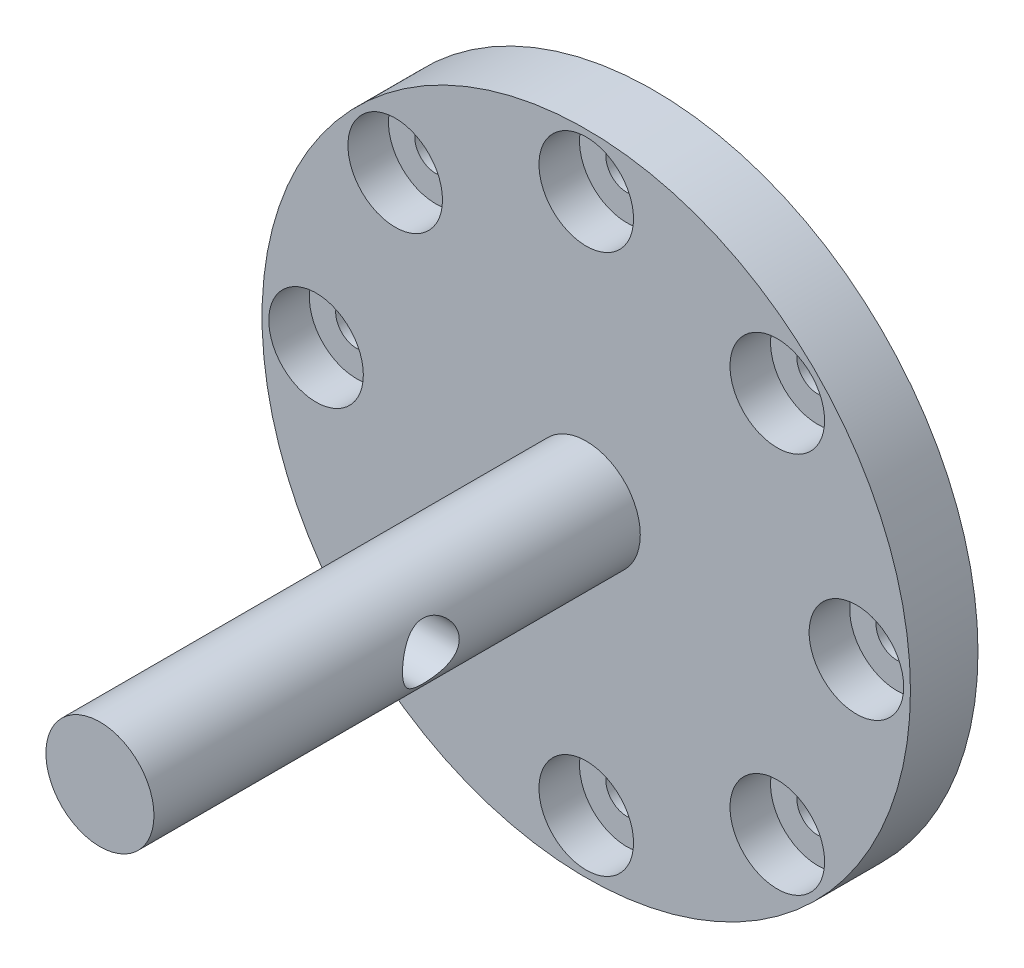
SolidWorks part; units mm, degrees
ref_plane "Front Plane" through (0, 0, 0) normal (0, 0, 1) x (1, 0, 0)
ref_plane "Top Plane" through (0, 0, 0) normal (0, 1, 0) x (1, 0, 0)
ref_plane "Right Plane" through (0, 0, 0) normal (1, 0, 0) x (0, 0, -1)
ref_axis "Axis1" through (0, 0, 5.5) along (0, 0, -1)
sketch "Sketch6" plane through (0, 0, 0) normal (0, 0, 1) x (1, 0, 0)
  circle A0 centre (0, 0) radius 24
extrude "Boss-Extrude1" add sketch "Sketch6" along normal blind 5
sketch "Sketch8" plane through (0, 0, 0) normal (0, 0, -1) x (-1, 0, 0)
  line L0 (0, 20) -> (0, 0) construction
  circle A0 centre (0, 20) radius 1.55
  circle A1 centre (14.1421, 14.1421) radius 1.55
  circle A2 centre (20, 0) radius 1.55
  circle A3 centre (14.1421, -14.1421) radius 1.55
  circle A4 centre (0, -20) radius 1.55
  circle A5 centre (-14.1421, -14.1421) radius 1.55
  circle A6 centre (-20, 0) radius 1.55
  circle A7 centre (-14.1421, 14.1421) radius 1.55
  dimension "D1" = 8
extrude "Cut-Extrude6" cut sketch "Sketch8" against normal up to surface (5 mm away) up to face at (24, 0, 5)
sketch "Sketch10" plane through (0, 0, 5) normal (0, 0, 1) x (1, 0, 0)
  circle A0 centre (0, 0) radius 4
extrude "Boss-Extrude2" add sketch "Sketch10" along normal blind 36
sketch "Sketch11" plane through (0, 0, 5) normal (0, 0, 1) x (1, 0, 0)
  circle A0 centre (0, 20) radius 3.5
  circle A1 centre (14.1421, 14.1421) radius 3.5
  circle A2 centre (20, 0) radius 3.5
  circle A3 centre (14.1421, -14.1421) radius 3.5
  circle A4 centre (0, -20) radius 3.5
  circle A5 centre (-14.1421, -14.1421) radius 3.5
  circle A6 centre (-20, 0) radius 3.5
  circle A7 centre (-14.1421, 14.1421) radius 3.5
  point P19 (0, 0)
  dimension "D1" = 8
extrude "Cut-Extrude8" cut sketch "Sketch11" against normal blind 3
ref_plane "Plane1" through (0, 0, 0) normal (1, 0, 0) x (0, 0, -1)
sketch "Sketch12" plane through (0, 0, 0) normal (1, 0, 0) x (0, 0, -1)
  line L0 (-41, 0) -> (-20.5, 0) construction
  line L2 (-41, 4) -> (-41, -4) construction
  circle A0 centre (-20.5, 0) radius 2.1
extrude "Cut-Extrude9" cut sketch "Sketch12" against normal up to surface and the other way up to surface up to face at (4, 0, 41) other way up to face at (4, 0, 41)
